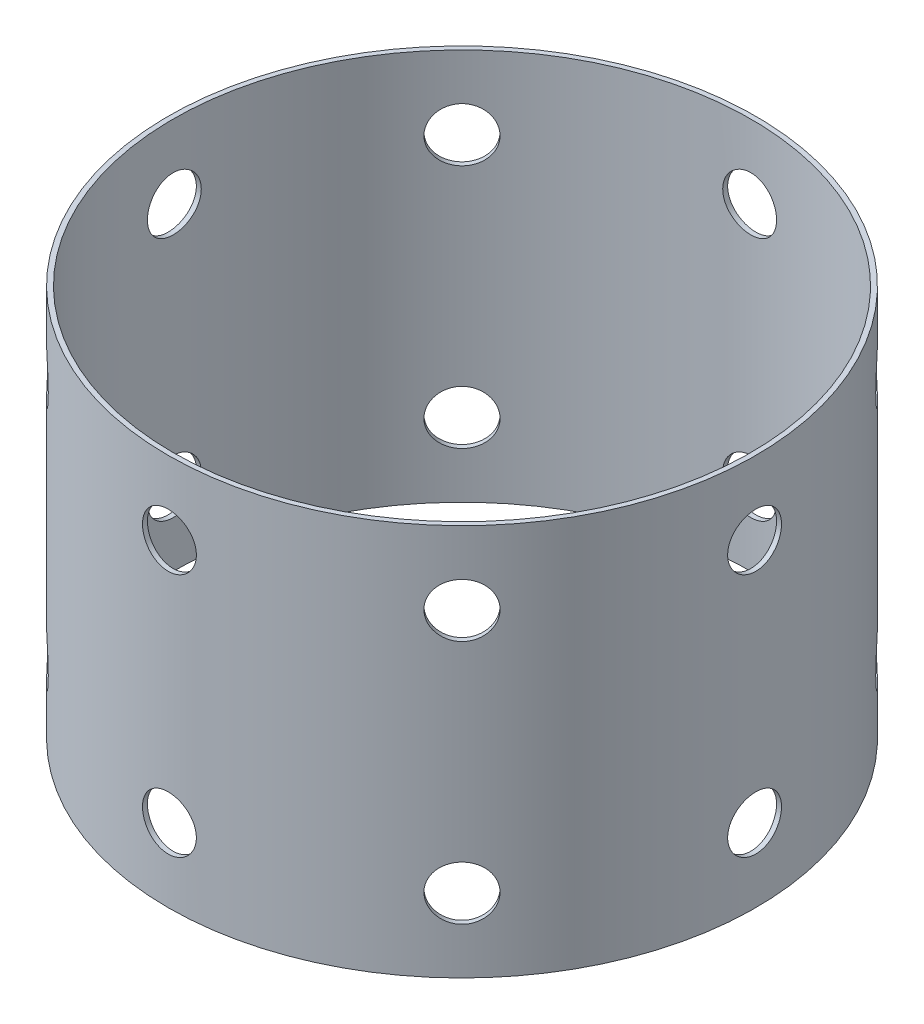
SolidWorks part; units mm, degrees
material "6061-T6 (SS)"
ref_plane "Front Plane" through (0, 0, 0) normal (0, 0, 1) x (1, 0, 0)
ref_plane "Top Plane" through (0, 0, 0) normal (0, 1, 0) x (1, 0, 0)
ref_plane "Right Plane" through (0, 0, 0) normal (1, 0, 0) x (0, 0, -1)
sketch "Sketch2" plane through (0, 0, 0) normal (0, 1, 0) x (1, 0, 0)
  circle A0 centre (0, 0) radius 74.93
  circle A1 centre (0, 0) radius 76.2
  dimension "D1" = 152.4
  dimension "D2" = 1.27
extrude "Boss-Extrude1" add sketch "Sketch2" along normal blind 101.6
sketch "Sketch3" plane through (0, 127, 0) normal (1, 0, 0) x (0, 0, -1)
  circle A0 centre (0, -44.45) radius 5.715 construction
  circle A1 centre (0, -44.45) radius 5.715 construction
  circle A2 centre (0, -44.45) radius 6.985
  dimension "D1" = 1.27
extrude "LOX to Kero, LOX Side Holes" cut sketch "Sketch3" along normal up to surface (75.8792 mm away) up to face at (0, 101.6, 76.2)
pattern_circular "CirPattern1" count 8 over 360 about axis through (0, 101.6, 0) along (0, 1, 0) of "LOX to Kero, LOX Side Holes"
sketch "Sketch4" plane through (0, -25.4, 0) normal (1, 0, 0) x (0, 0, 1)
  circle A0 centre (0, -44.45) radius 5.715 construction
  circle A1 centre (0, -44.45) radius 5.715 construction
  circle A2 centre (0, -44.45) radius 6.985
  dimension "D1" = 1.27
extrude "LOX to Kero, Kero Side Holes" cut sketch "Sketch4" along normal up to surface (75.8792 mm away) up to face at (0, 101.6, 76.2)
pattern_circular "CirPattern2" count 8 over 360 about axis through (0, 0, 0) along (0, 1, 0) of "LOX to Kero, Kero Side Holes"
sketch "Sketch5" [suppressed] plane through (0, -25.4, 0) normal (1, 0, 0) x (0, 0, 1)
  circle A0 centre (0, -38.1) radius 5.715 construction
  circle A1 centre (0, -38.1) radius 5.715 construction
  circle A2 centre (0, -38.1) radius 6.985
  dimension "D1" = 1.27
extrude "N2 to LOX, LOX Side Holes" [suppressed] cut sketch "Sketch5" along normal up to surface (75.8792 mm away) up to face at (0, 101.6, 76.2)
pattern_circular "CirPattern3" [suppressed] count 8 over 360 reverse direction yes of bodies 107
